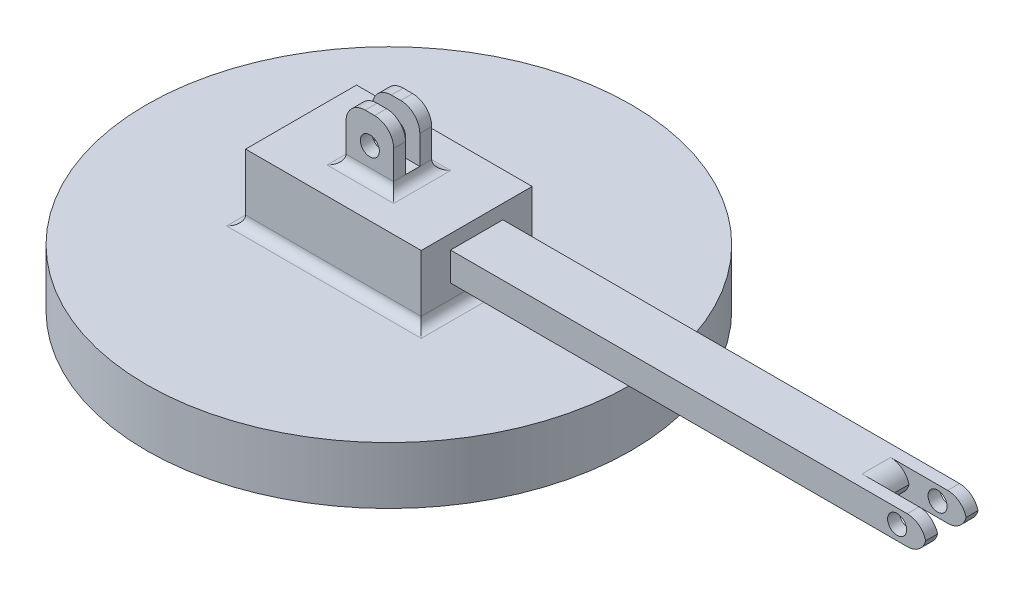
SolidWorks part; units mm, degrees
ref_plane "Front Plane" through (0, 0, 0) normal (0, 0, 1) x (1, 0, 0)
ref_plane "Top Plane" through (0, 0, 0) normal (0, 1, 0) x (1, 0, 0)
ref_plane "Right Plane" through (0, 0, 0) normal (1, 0, 0) x (0, 0, -1)
sketch "Sketch1" plane through (0, 0, 0) normal (0, 1, 0) x (1, 0, 0)
  circle A0 centre (0, 0) radius 25.48
  dimension "D1" = 50.96
extrude "Boss-Extrude1" add sketch "Sketch1" along normal blind 6
sketch "Sketch2" plane through (0, 6, 0) normal (0, 1, 0) x (1, 0, 0)
  line L1 (-9.2274, 5.8288) -> (9.2274, 5.8288)
  line L2 (-9.2274, 5.8288) -> (-9.2274, -5.8288)
  line L3 (-9.2274, -5.8288) -> (9.2274, -5.8288)
  line L4 (9.2274, 5.8288) -> (9.2274, -5.8288)
  line L5 (-9.2274, 5.8288) -> (9.2274, -5.8288) construction
  line L6 (-9.2274, -5.8288) -> (9.2274, 5.8288) construction
  point P1 (0, 0)
extrude "Boss-Extrude2" add sketch "Sketch2" along normal blind 7
fillet "Fillet1" radius 1 4 edges at (-9.2274, 6, 0) (0, 6, 5.8288) (0, 6, -5.8288) (9.2274, 6, 0)
sketch "Sketch3" plane through (9.2274, 0, 0) normal (1, 0, 0) x (0, 0, -1)
  line L1 (-2.75, 11.5) -> (2.75, 11.5)
  line L2 (-2.75, 11.5) -> (-2.75, 8.5)
  line L3 (-2.75, 8.5) -> (2.75, 8.5)
  line L4 (2.75, 11.5) -> (2.75, 8.5)
  line L5 (-2.75, 11.5) -> (2.75, 8.5) construction
  line L6 (-2.75, 8.5) -> (2.75, 11.5) construction
  line L10 (0, 13) -> (0, 7) construction
  line L11 (-5.8288, 13) -> (5.8288, 13) construction
  line L12 (-5.8288, 7) -> (5.8288, 7) construction
  line L13 (-5.8288, 10) -> (5.8288, 10) construction
  line L14 (-5.8288, 13) -> (-5.8288, 7) construction
  line L15 (5.8288, 13) -> (5.8288, 7) construction
  point P0 (0, 10)
  point P17 (0, 10)
  dimension "D1" = 3
  dimension "D2" = 5.5
extrude "Boss-Extrude3" add sketch "Sketch3" along normal blind 50 separate body
sketch "Sketch7" plane through (0, 11.5, 0) normal (0, 1, 0) x (1, 0, 0)
  line L0 (59.2274, 0) -> (40.8826, 0) construction
  line L1 (59.2274, 2.75) -> (59.2274, -2.75) construction
  line L3 (53.2274, 1.5) -> (59.2274, 1.5)
  line L4 (53.2274, 1.5) -> (53.2274, -1.5)
  line L5 (53.2274, -1.5) -> (59.2274, -1.5)
  line L6 (59.2274, 1.5) -> (59.2274, -1.5)
  line L7 (53.2274, 1.5) -> (59.2274, -1.5) construction
  line L8 (53.2274, -1.5) -> (59.2274, 1.5) construction
  point P5 (56.2274, 0)
  dimension "D1" = 3
  dimension "D2" = 6
extrude "Cut-Extrude3" cut sketch "Sketch7" against normal through all
fillet "Fillet3" radius 2 4 edges at (59.2274, 8.5, 2.125) (59.2274, 11.5, 2.125) (59.2274, 8.5, -2.125) (59.2274, 11.5, -2.125)
sketch "Sketch9" plane through (0, 13, 0) normal (0, 1, 0) x (1, 0, 0)
  line L1 (-2.5, 2) -> (2.5, 2)
  line L2 (-2.5, 2) -> (-2.5, -2)
  line L3 (-2.5, -2) -> (2.5, -2)
  line L4 (2.5, 2) -> (2.5, -2)
  line L5 (-2.5, 2) -> (2.5, -2) construction
  line L6 (-2.5, -2) -> (2.5, 2) construction
  point P0 (0, 0)
  dimension "D1" = 5
  dimension "D2" = 4
extrude "Boss-Extrude4" add sketch "Sketch9" along normal blind 6
fillet "Fillet4" radius 1 4 edges at (0, 13, 2) (2.5, 13, 0) (0, 13, -2) (-2.5, 13, 0)
sketch "Sketch10" plane through (0, 19, 0) normal (0, 1, 0) x (1, 0, 0)
  line L1 (-4.5301, 0.75) -> (4.5301, 0.75)
  line L2 (-4.5301, 0.75) -> (-4.5301, -0.75)
  line L3 (-4.5301, -0.75) -> (4.5301, -0.75)
  line L4 (4.5301, 0.75) -> (4.5301, -0.75)
  line L5 (-4.5301, 0.75) -> (4.5301, -0.75) construction
  line L6 (-4.5301, -0.75) -> (4.5301, 0.75) construction
  point P0 (0, 0)
  dimension "D1" = 1.5
extrude "Cut-Extrude5" cut sketch "Sketch10" against normal blind 5
sketch "Sketch11" plane through (0, 0, -2) normal (0, 0, -1) x (-1, 0, 0)
  line L0 (-2.5, 19) -> (2.5, 19) construction
  circle A0 centre (0, 16) radius 1
  dimension "D1" = 2
  dimension "D2" = 3
extrude "Cut-Extrude6" cut sketch "Sketch11" against normal through all
fillet "Fillet5" radius 2 4 edges at (2.5, 19, 1.375) (-2.5, 19, 1.375) (2.5, 19, -1.375) (-2.5, 19, -1.375)
fillet "Fillet6" radius 2 2 edges at (53.2274, 8.5, 0) (53.2274, 11.5, 0)
sketch "Sketch13" plane through (0, 0, -2.75) normal (0, 0, -1) x (-1, 0, 0)
  circle A0 centre (-56.1639, 10) radius 1
  dimension "D2" = 2
  dimension "D1" = 3
extrude "Cut-Extrude7" cut sketch "Sketch13" against normal through all
